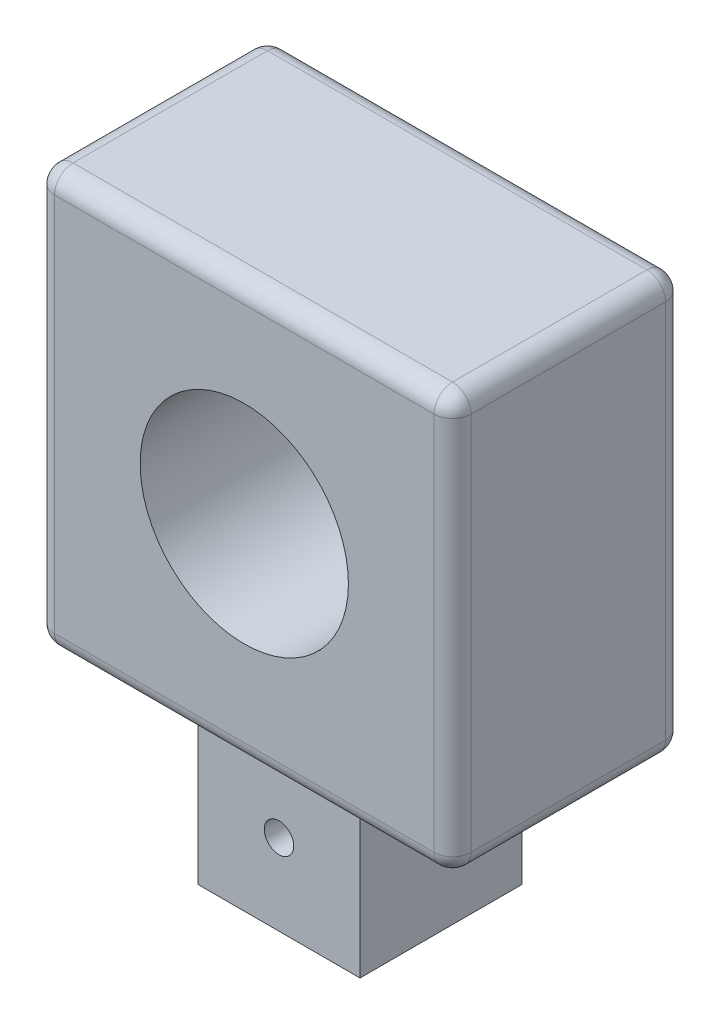
SolidWorks part; units mm, degrees
ref_plane "Front Plane" through (0, 0, 0) normal (0, 0, 1) x (1, 0, 0)
ref_plane "Top Plane" through (0, 0, 0) normal (0, 1, 0) x (1, 0, 0)
ref_plane "Right Plane" through (0, 0, 0) normal (1, 0, 0) x (0, 0, -1)
sketch "Sketch1" plane through (0, 0, 0) normal (0, 1, 0) x (1, 0, 0)
  line L1 (-11.1125, -11.1125) -> (11.1125, -11.1125)
  line L2 (-11.1125, -11.1125) -> (-11.1125, 11.1125)
  line L3 (-11.1125, 11.1125) -> (11.1125, 11.1125)
  line L4 (11.1125, -11.1125) -> (11.1125, 11.1125)
  line L5 (-11.1125, -11.1125) -> (11.1125, 11.1125) construction
  line L6 (-11.1125, 11.1125) -> (11.1125, -11.1125) construction
  point P0 (0, 0)
  dimension "D1" = 22.225
  dimension "D2" = 22.225
extrude "Boss-Extrude1" add sketch "Sketch1" along normal blind 12.7 and the other way blind 9.525
sketch "Sketch2" plane through (0, 12.7, 0) normal (0, 1, 0) x (1, 0, 0)
  line L1 (-28.575, -15.875) -> (28.575, -15.875)
  line L2 (-28.575, -15.875) -> (-28.575, 15.875)
  line L3 (-28.575, 15.875) -> (28.575, 15.875)
  line L4 (28.575, -15.875) -> (28.575, 15.875)
  line L5 (-28.575, -15.875) -> (28.575, 15.875) construction
  line L6 (-28.575, 15.875) -> (28.575, -15.875) construction
  point P0 (0, 0)
  dimension "D1" = 57.15
  dimension "D2" = 31.75
extrude "Boss-Extrude2" add sketch "Sketch2" along normal blind 57.15
sketch "Sketch3" plane through (0, 0, 15.875) normal (0, 0, 1) x (1, 0, 0)
  line L0 (-28.575, 69.85) -> (28.575, 69.85) construction
  line L1 (28.575, 69.85) -> (28.575, 12.7) construction
  circle A0 centre (0, 41.275) radius 14.2875
  dimension "D1" = 28.575
  dimension "D2" = 28.575
  dimension "D3" = 28.575
extrude "Cut-Extrude1" cut sketch "Sketch3" against normal through all
fillet "Fillet1" radius 2.54 12 edges at (28.575, 69.85, 0) (28.575, 12.7, 0) (-28.575, 69.85, 0) (-28.575, 12.7, 0) (28.575, 41.275, -15.875) (0, 69.85, -15.875) (-28.575, 41.275, -15.875) (0, 12.7, -15.875) (-28.575, 41.275, 15.875) (0, 69.85, 15.875) (28.575, 41.275, 15.875) (0, 12.7, 15.875)
sketch "Sketch4" plane through (0, 0, -11.1125) normal (0, 0, -1) x (-1, 0, 0)
  line L0 (-11.1125, -9.525) -> (11.1125, -9.525) construction
  line L1 (-11.1125, -9.525) -> (-11.1125, 12.7) construction
  circle A0 centre (0, 1.5875) radius 2.0193
  dimension "D1" = 4.0386
  dimension "D2" = 11.1125
  dimension "D3" = 11.1125
extrude "Cut-Extrude2" cut sketch "Sketch4" against normal through all
